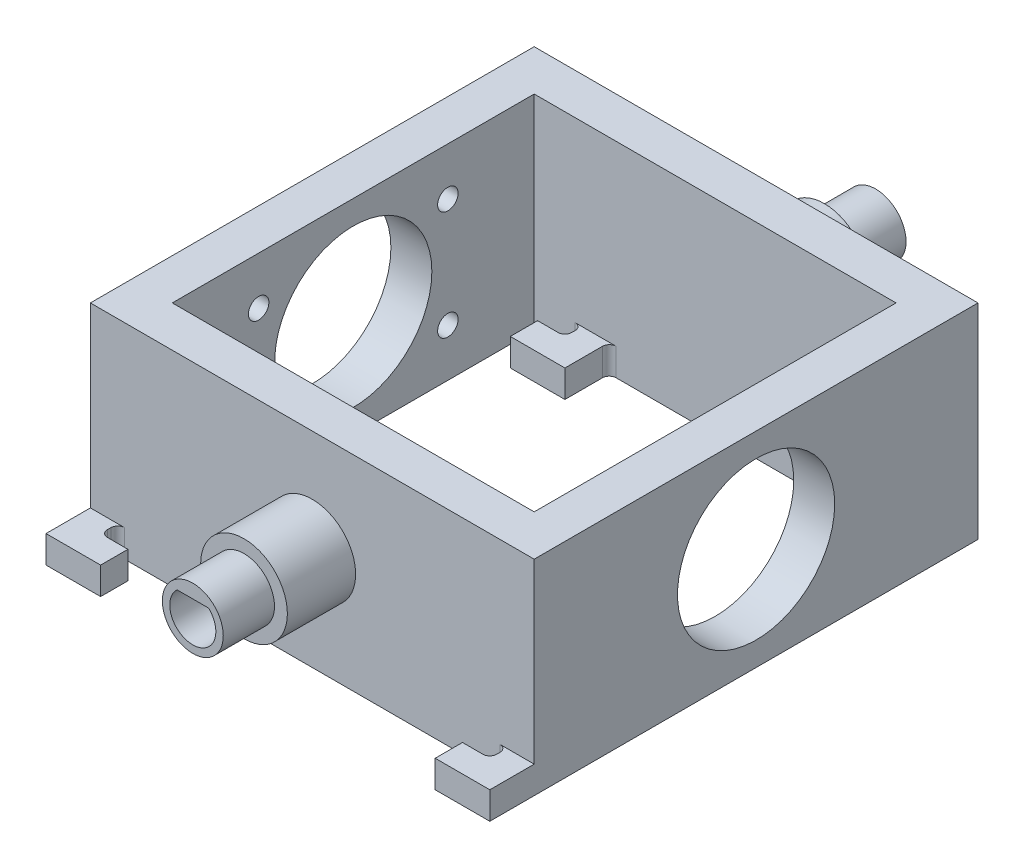
SolidWorks part; units mm, degrees
ref_plane "Front Plane" through (0, 0, 0) normal (0, 0, 1) x (1, 0, 0)
ref_plane "Top Plane" through (0, 0, 0) normal (0, 1, 0) x (1, 0, 0)
ref_plane "Right Plane" through (0, 0, 0) normal (1, 0, 0) x (0, 0, -1)
sketch "Sketch1" plane through (0, 0, 0) normal (0, 1, 0) x (1, 0, 0)
  line L0 (6, 6) -> (6, 59)
  line L1 (0, 0) -> (65, 0)
  line L2 (0, 0) -> (0, 65)
  line L3 (0, 65) -> (65, 65)
  line L4 (65, 0) -> (65, 65)
  line L5 (6, 59) -> (59, 59)
  line L6 (59, 6) -> (59, 59)
  line L7 (6, 6) -> (59, 6)
  dimension "D1" = 65
  dimension "D2" = 65
  dimension "D3" = 6
extrude "Boss-Extrude1" add sketch "Sketch1" along normal blind 30
sketch "Sketch2" plane through (0, 0, 0) normal (0, 0, 1) x (1, 0, 0)
  line L0 (32.5, 30) -> (32.5, 0) construction
  line L1 (0, 30) -> (65, 30) construction
  line L2 (0, 0) -> (65, 0) construction
  line L3 (65, 15) -> (0, 15) construction
  line L4 (65, 30) -> (65, 0) construction
  line L5 (0, 30) -> (0, 0) construction
  circle A0 centre (32.5, 15) radius 4.4625
  dimension "D1" = 8.925
sketch "Sketch3" plane through (65, 0, 0) normal (1, 0, 0) x (0, 0, -1)
  line L0 (0, 15) -> (65, 15) construction
  line L1 (0, 30) -> (0, 0) construction
  line L2 (65, 30) -> (65, 0) construction
  line L3 (32.5, 30) -> (32.5, 0) construction
  line L4 (0, 30) -> (65, 30) construction
  line L5 (0, 0) -> (65, 0) construction
  circle A0 centre (32.5, 15) radius 11.5125
  dimension "D1" = 23.025
extrude "Cut-Extrude2" cut sketch "Sketch3" against normal through all
extrude "Boss-Extrude2" add sketch "Sketch2" along normal blind 17.5
extrude "Boss-Extrude3" add sketch "Sketch2<2>" against normal blind 17.5 from surface starting at face at (32.5, 15, -65)
sketch "Sketch2<2>" plane through (0, 0, 0) normal (0, 0, 1) x (1, 0, 0) same geometry as "Sketch2"
sketch "Sketch4" plane through (0, 0, 17.5) normal (0, 0, 1) x (1, 0, 0)
  line L0 (30.185, 17.4559) -> (34.815, 17.4559)
  line L1 (32.5, 17.4559) -> (32.5, 11.625) construction
  line L2 (29.125, 15) -> (35.875, 15) construction
  arc A0 (30.185, 17.4559) -> (34.815, 17.4559) centre (32.5, 15) ccw
  circle A1 centre (32.5, 15) radius 4.4625 construction
  circle A2 centre (32.5, 15) radius 4.4625
  dimension "D1" = 6.75
  dimension "D2" = 4.63
extrude "Cut-Extrude3" cut sketch "Sketch4" against normal up to next contours L0 A0
sketch "Sketch5" plane through (0, 0, 0) normal (0, 0, 1) x (1, 0, 0)
  circle A0 centre (32.5, 15) radius 6.35
  circle A3 centre (32.5, 15) radius 4.4625
  circle A4 centre (32.5, 15) radius 4.4625
  dimension "D1" = 12.7
  dimension "D2" = 0
extrude "Boss-Extrude4" add sketch "Sketch5" along normal blind 10
sketch "Sketch6" plane through (0, 0, -65) normal (0, 0, -1) x (-1, 0, 0)
  circle A0 centre (-32.5, 15) radius 6.35
  circle A3 centre (-32.5, 15) radius 4.4625
  circle A4 centre (-32.5, 15) radius 4.4625
  dimension "D1" = 12.7
  dimension "D2" = 0
extrude "Boss-Extrude5" add sketch "Sketch6" along normal blind 10
sketch "Sketch7" plane through (0, 0, 0) normal (-1, 0, 0) x (0, 0, 1)
  line L0 (-32.5, 15) -> (-46.3564, 23) construction
  line L1 (-32.5, 15) -> (-32.5, 29.3091) construction
  line L2 (-32.5, 15) -> (-47.7046, 15) construction
  circle A0 centre (-46.3564, 23) radius 1.5
  circle A1 centre (-32.5, 15) radius 11.5125 construction
  circle A2 centre (-32.5, 15) radius 11.5125 construction
  circle A3 centre (-46.3564, 7) radius 1.5
  circle A4 centre (-18.6436, 23) radius 1.5
  circle A5 centre (-18.6436, 7) radius 1.5
  dimension "D3" = 3
  dimension "D1" = 60
  dimension "D2" = 16
extrude "Cut-Extrude4" cut sketch "Sketch7" against normal blind 10
sketch "Sketch8" plane through (30, 30, 0) normal (0, -1, 0) x (0, 0, 1)
  line L7 (0, -35) -> (-65, -35) construction
  line L8 (0, -35) -> (6.5, -35)
  line L9 (0, -35) -> (0, -31)
  line L10 (0, -31) -> (2.5, -31)
  line L11 (6.5, -35) -> (6.5, -31)
  line L12 (6.5, -31) -> (6.5, -27)
  line L13 (6.5, -27) -> (2.5, -27)
  line L14 (2.5, -27) -> (2.5, -31)
  line L15 (0, -27) -> (2.5, -27) construction
  line L16 (0, 30) -> (0, -35) construction
  point P0 (-49.2438, -29)
  dimension "D5" = 4
  dimension "D6" = 4
  dimension "D7" = 2.5
  dimension "D8" = 4
  dimension "D9" = 4
extrude "Boss-Extrude6" add sketch "Sketch8" against normal blind 4 from surface starting at face at (32.5, 0, -32.5)
sketch "Sketch9" plane through (0, 0, 0) normal (0, -1, 0) x (1, 0, 0)
  line L0 (17, -59) -> (17, -52.5)
  line L1 (17, -59) -> (13, -59)
  line L2 (13, -59) -> (13, -56.5)
  line L3 (17, -52.5) -> (13, -52.5)
  line L4 (13, -52.5) -> (9, -52.5)
  line L5 (9, -52.5) -> (9, -56.5)
  line L6 (9, -56.5) -> (13, -56.5)
  line L7 (9, -56.9468) -> (9, -56.5) construction
  line L8 (59, -59) -> (6, -59) construction
  line L9 (6, -59) -> (6, -6) construction
  point P8 (12.9568, -59)
  dimension "D1" = 4
  dimension "D2" = 4
  dimension "D3" = 2.5
  dimension "D4" = 4
  dimension "D5" = 4
  dimension "D6" = 3
extrude "Boss-Extrude8" add sketch "Sketch9" against normal blind 4
ref_plane "Plane1" through (32.5, 0, 0) normal (-1, 0, 0) x (0, 0, 1)
ref_plane "Plane2" through (0, 0, -32.5) normal (0, 0, 1) x (1, 0, 0)
mirror "Mirror1" about plane through (32.5, 0, 0) normal (-1, 0, 0) of "Boss-Extrude6"
mirror "Mirror2" about plane through (0, 0, -32.5) normal (0, 0, 1) of "Boss-Extrude8"
fillet "Fillet3" radius 1 10 edges at (61, 2, 2.5) (61, 2, 0) (4, 2, 2.5) (4, 2, 0) (13, 2, -59) (13, 2, -56.5) (13, 2, -6) (13, 2, -8.5) (17, 2, -6) (17, 2, -59)
